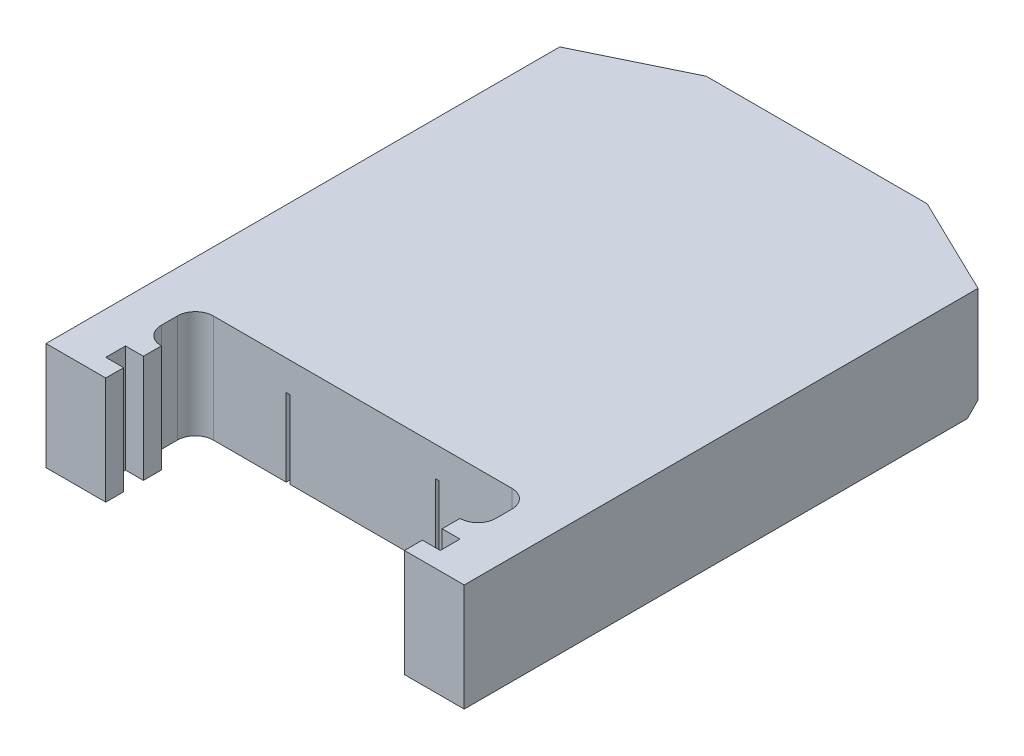
SolidWorks part; units mm, degrees
ref_plane "前视基准面" through (0, 0, 0) normal (0, 0, 1) x (1, 0, 0)
ref_plane "上视基准面" through (0, 0, 0) normal (0, 1, 0) x (1, 0, 0)
ref_plane "右视基准面" through (0, 0, 0) normal (1, 0, 0) x (0, 0, -1)
sketch "草图1" plane through (0, 0, 0) normal (0, 0, 1) x (1, 0, 0)
  line L1 (0, 0) -> (70, 0)
  line L2 (0, 0) -> (0, 18)
  line L3 (0, 18) -> (70, 18)
  line L4 (70, 0) -> (70, 18)
  dimension "D1" = 70
  dimension "D2" = 18
extrude "凸台-拉伸1" add sketch "草图1" along normal blind 60
sketch "草图2" plane through (0, 0, 60) normal (0, 0, 1) x (1, 0, 0)
  line L0 (13.4, 0) -> (13.4, 5.3)
  line L1 (0, 0) -> (70, 0) construction
  line L2 (13.4, 5.3) -> (9.4, 5.3)
  line L3 (35, 18) -> (35, 0) construction
  line L4 (70, 18) -> (0, 18) construction
  line L5 (9.4, 5.3) -> (9.4, 12)
  line L6 (9.4, 12) -> (60.6, 12)
  line L7 (13.4, 0) -> (56.6, 0)
  line L8 (60.6, 5.3) -> (60.6, 12)
  line L9 (56.6, 5.3) -> (60.6, 5.3)
  line L10 (56.6, 0) -> (56.6, 5.3)
  point P11 (35, 12)
  dimension "D1" = 25.6
  dimension "D2" = 12
  dimension "D3" = 5.3
  dimension "D4" = 4
extrude "切除-拉伸1" cut sketch "草图2" against normal through all
sketch "草图3" plane through (13.4, 0, 0) normal (1, 0, 0) x (0, 0, -1)
  line L0 (0, 0) -> (-60, 0) construction
  line L1 (0, 5.3) -> (-15, 5.3)
  line L2 (0, 5.3) -> (0, 0)
  line L3 (0, 0) -> (-15, 0)
  line L4 (-15, 5.3) -> (-15, 0)
  line L5 (-60, 5.3) -> (-60, 0) construction
  dimension "D1" = 45
extrude "切除-拉伸2" cut sketch "草图3" against normal blind 1
sketch "草图4" plane through (56.6, 0, 0) normal (-1, 0, 0) x (0, 0, 1)
  line L0 (0, 5.3) -> (60, 5.3) construction
  line L1 (0, 0) -> (15, 0)
  line L2 (0, 0) -> (0, 5.3)
  line L3 (0, 5.3) -> (15, 5.3)
  line L4 (15, 0) -> (15, 5.3)
  line L5 (60, 0) -> (60, 5.3) construction
  dimension "D1" = 45
extrude "切除-拉伸3" cut sketch "草图4" against normal blind 1
sketch "草图5" plane through (0, 5.3, 0) normal (0, 1, 0) x (1, 0, 0)
  line L0 (57.6, -15) -> (57.6, 0) construction
  line L1 (60.6, 0) -> (57.6, 0)
  line L2 (60.6, 0) -> (60.6, -11)
  line L3 (60.6, -11) -> (57.6, -11)
  line L4 (57.6, 0) -> (57.6, -11)
  line L5 (57.6, -15) -> (56.6, -15) construction
  dimension "D1" = 4
extrude "切除-拉伸4" cut sketch "草图5" against normal blind 1
sketch "草图6" plane through (0, 5.3, 0) normal (0, 1, 0) x (1, 0, 0)
  line L0 (12.4, 0) -> (12.4, -15) construction
  line L1 (9.4, 0) -> (12.4, 0)
  line L2 (9.4, 0) -> (9.4, -11)
  line L3 (9.4, -11) -> (12.4, -11)
  line L4 (12.4, 0) -> (12.4, -11)
  line L5 (12.4, -15) -> (13.4, -15) construction
  dimension "D1" = 4
extrude "切除-拉伸5" cut sketch "草图6" against normal blind 1
chamfer "倒角1" distance 1 angle 45 4 edges at (59.1, 4.3, 11) (10.9, 4.3, 11) (12.4, 2.65, 15) (57.6, 2.65, 15)
sketch "草图21" plane through (0, 18, 0) normal (0, 1, 0) x (1, 0, 0)
  line L0 (0, 0) -> (16.5, 8)
  line L1 (16.5, 8) -> (53.5, 8)
  line L2 (53.5, 8) -> (70, 0)
  line L3 (0, -60) -> (0, 0) construction
  line L4 (70, 0) -> (0, 0) construction
  line L5 (0, 0) -> (70, 0)
  dimension "D1" = 37
  dimension "D2" = 16.5
  dimension "D3" = 8
extrude "凸台-拉伸9" add sketch "草图21" against normal blind 6
sketch "草图7" plane through (0, 12, 0) normal (0, -1, 0) x (1, 0, 0)
  line L0 (60.6, 60) -> (9.4, 60) construction
  line L1 (20.25, -4) -> (49.75, -4)
  line L2 (20.25, -4) -> (20.25, 5)
  line L3 (20.25, 5) -> (49.75, 5)
  line L4 (49.75, -4) -> (49.75, 5)
  line L5 (35, 60) -> (35, -8) construction
  line L6 (53.5, -8) -> (16.5, -8) construction
  dimension "D1" = 29.5
  dimension "D2" = 9
  dimension "D3" = 55
  dimension "D4" = 14.75
extrude "切除-拉伸7" cut sketch "草图7" against normal blind 4
sketch "草图9" plane through (0, 12, 0) normal (0, -1, 0) x (1, 0, 0)
  line L0 (60.6, 60) -> (9.4, 60) construction
  line L1 (16.5, 60) -> (53.5, 60)
  line L2 (16.5, 60) -> (16.5, 52.5)
  line L3 (16.5, 52.5) -> (53.5, 52.5)
  line L4 (53.5, 60) -> (53.5, 52.5)
  line L5 (35, 60) -> (35, -8) construction
  line L7 (53.5, -8) -> (16.5, -8) construction
  dimension "D1" = 37
  dimension "D2" = 7.5
extrude "凸台-拉伸3" add sketch "草图9" along normal blind 12
sketch "草图10" plane through (0, 0, 60) normal (0, 0, 1) x (1, 0, 0)
  line L1 (0, 0) -> (70, 0)
  line L2 (0, 0) -> (0, 18)
  line L3 (0, 18) -> (70, 18)
  line L4 (70, 0) -> (70, 18)
extrude "凸台-拉伸4" add sketch "草图10" along normal blind 8
chamfer "倒角4" distance 4 angle 45 1 edges at (35, 16, 5)
sketch "草图11" plane through (0, 0, 0) normal (0, -1, 0) x (1, 0, 0)
  line L0 (16.5, 52.5) -> (53.5, 52.5) construction
  line L1 (31, 52.5) -> (39, 52.5)
  line L2 (31, 52.5) -> (31, 63.5)
  line L3 (31, 63.5) -> (39, 63.5)
  line L4 (39, 52.5) -> (39, 63.5)
  line L5 (35, 68) -> (35, 52.5) construction
  line L6 (0, 68) -> (70, 68) construction
  dimension "D1" = 8
  dimension "D2" = 11
  dimension "D3" = 4
extrude "切除-拉伸8" cut sketch "草图11" against normal blind 3
sketch "草图12" plane through (0, 0, 0) normal (0, -1, 0) x (1, 0, 0)
  line L0 (16.5, 52.5) -> (31, 52.5) construction
  line L1 (22.2, 34.5) -> (22.8, 34.5)
  line L2 (22.2, 34.5) -> (22.2, 68)
  line L3 (22.2, 68) -> (22.8, 68)
  line L4 (22.8, 34.5) -> (22.8, 68)
  line L5 (0, 68) -> (70, 68) construction
  line L6 (39, 52.5) -> (53.5, 52.5) construction
  line L7 (47.2, 34.5) -> (47.8, 34.5)
  line L8 (47.2, 34.5) -> (47.2, 68)
  line L9 (47.2, 68) -> (47.8, 68)
  line L10 (47.8, 34.5) -> (47.8, 68)
  line L11 (35, 68) -> (35, 52.5) construction
  line L12 (16.5, 52.5) -> (53.5, 52.5) construction
  dimension "D1" = 0.6
  dimension "D2" = 0.6
  dimension "D3" = 24.4
  dimension "D4" = 12.2
  dimension "D5" = 18
  dimension "D6" = 18
extrude "切除-拉伸9" cut sketch "草图12" against normal blind 13
sketch "草图13" plane through (0, 12, 0) normal (0, -1, 0) x (1, 0, 0)
  line L1 (17.1, 0) -> (16.5, 0)
  line L2 (17.1, 0) -> (17.1, 52.5)
  line L3 (17.1, 52.5) -> (16.5, 52.5)
  line L4 (16.5, 0) -> (16.5, 52.5)
  line L5 (53.5, 52.5) -> (52.9, 52.5)
  line L6 (53.5, 52.5) -> (53.5, 0)
  line L7 (53.5, 0) -> (52.9, 0)
  line L8 (52.9, 52.5) -> (52.9, 0)
  dimension "D1" = 0.6
  dimension "D2" = 0.6
  dimension "D3" = 52.5
  dimension "D4" = 52.5
extrude "凸台-拉伸5" add sketch "草图13" along normal blind 6.7
sketch "草图14" plane through (0, 5.3, 0) normal (0, -1, 0) x (1, 0, 0)
  line L0 (17.1, 0) -> (17.1, 52.5) construction
  line L1 (16.5, 0) -> (17.1, 0)
  line L2 (16.5, 0) -> (16.5, 10)
  line L3 (16.5, 10) -> (17.1, 10)
  line L4 (17.1, 0) -> (17.1, 10)
  line L5 (52.9, 52.5) -> (52.9, 0) construction
  line L6 (53.5, 0) -> (52.9, 0)
  line L7 (53.5, 0) -> (53.5, 10)
  line L8 (53.5, 10) -> (52.9, 10)
  line L9 (52.9, 0) -> (52.9, 10)
  line L10 (9.4, 10) -> (12.4, 10) construction
  line L11 (57.6, 10) -> (60.6, 10) construction
extrude "凸台-拉伸6" add sketch "草图14" along normal blind 1
sketch "草图15" plane through (0, 5.3, 0) normal (0, -1, 0) x (1, 0, 0)
  line L0 (17.1, 10) -> (17.1, 52.5) construction
  line L1 (17.1, 11) -> (9.4, 11)
  line L2 (17.1, 11) -> (17.1, 60)
  line L3 (17.1, 60) -> (9.4, 60)
  line L4 (9.4, 11) -> (9.4, 60)
  line L5 (52.9, 11) -> (60.6, 11)
  line L6 (52.9, 11) -> (52.9, 60)
  line L7 (52.9, 60) -> (60.6, 60)
  line L8 (60.6, 11) -> (60.6, 60)
  line L9 (9.4, 11) -> (12.4, 11) construction
  line L10 (52.9, 52.5) -> (52.9, 10) construction
  line L11 (57.6, 11) -> (60.6, 11) construction
extrude "凸台-拉伸7" add sketch "草图15" along normal blind 0.6
sketch "草图18" plane through (0, 4.3, 0) normal (0, -1, 0) x (1, 0, 0)
  line L0 (9.4, 11) -> (9.4, 10) construction
  line L1 (17.1, 0) -> (9.4, 0)
  line L2 (17.1, 0) -> (17.1, 10)
  line L3 (17.1, 10) -> (9.4, 10)
  line L4 (9.4, 0) -> (9.4, 10)
  line L5 (9.4, 10) -> (12.4, 10) construction
  line L6 (57.6, 10) -> (60.6, 10) construction
  line L7 (52.9, 0) -> (60.6, 0)
  line L8 (52.9, 0) -> (52.9, 10)
  line L9 (52.9, 10) -> (60.6, 10)
  line L10 (60.6, 0) -> (60.6, 10)
extrude "凸台-拉伸8" add sketch "草图18" along normal blind 0.6
chamfer "倒角5" distance 1.8 angle 45 5 edges at (63.8, 0, 0) (6.2, 0, 0) (35, 12, -8)
sketch "草图22" plane through (0, 0, 0) normal (0, -1, 0) x (1, 0, 0)
  line L0 (22.8, 52.5) -> (22.8, 68) construction
  line L1 (22.8, 57.5) -> (25.8, 57.5)
  line L2 (22.8, 57.5) -> (22.8, 64)
  line L3 (22.8, 64) -> (25.8, 64)
  line L4 (25.8, 57.5) -> (25.8, 64)
  line L5 (47.2, 68) -> (47.2, 52.5) construction
  line L6 (47.2, 57.5) -> (44.2, 57.5)
  line L7 (47.2, 57.5) -> (47.2, 64)
  line L8 (47.2, 64) -> (44.2, 64)
  line L9 (44.2, 57.5) -> (44.2, 64)
  line L10 (22.8, 52.5) -> (31, 52.5) construction
  line L11 (39, 52.5) -> (47.2, 52.5) construction
  dimension "D1" = 6.5
  dimension "D2" = 6.5
  dimension "D3" = 3
  dimension "D4" = 3
  dimension "D5" = 5
  dimension "D6" = 5
extrude "切除-拉伸10" cut sketch "草图22" against normal blind 1
sketch "草图23" plane through (0, 18, 0) normal (0, 1, 0) x (1, 0, 0)
  line L0 (0, -68) -> (0, -86)
  line L1 (0, -86) -> (10, -86)
  line L2 (10, -86) -> (10, -83)
  line L3 (10, -83) -> (7, -83)
  line L4 (7, -83) -> (7, -79.7)
  line L5 (7, -79.7) -> (10, -79.7)
  line L6 (10, -79.7) -> (10, -76.7)
  line L7 (10, -76.7) -> (7, -76.7)
  line L8 (7, -76.7) -> (7, -68)
  line L9 (70, -68) -> (0, -68) construction
  line L10 (35, 8) -> (35, -68) construction
  line L11 (53.5, 8) -> (16.5, 8) construction
  line L12 (63, -68) -> (70, -68)
  line L13 (63, -76.7) -> (63, -68)
  line L14 (60, -76.7) -> (63, -76.7)
  line L15 (60, -79.7) -> (60, -76.7)
  line L16 (63, -79.7) -> (60, -79.7)
  line L17 (63, -83) -> (63, -79.7)
  line L18 (60, -83) -> (63, -83)
  line L19 (60, -86) -> (60, -83)
  line L20 (70, -86) -> (60, -86)
  line L21 (7, -68) -> (0, -68)
  line L22 (70, -68) -> (70, -86)
  dimension "D1" = 10
  dimension "D2" = 18
  dimension "D3" = 3
  dimension "D4" = 3
  dimension "D5" = 3
  dimension "D6" = 3.3
extrude "凸台-拉伸10" add sketch "草图23" against normal blind 18
fillet "圆角1" radius 3 4 edges at (7, 9, 76.7) (63, 9, 68) (63, 9, 76.7)
